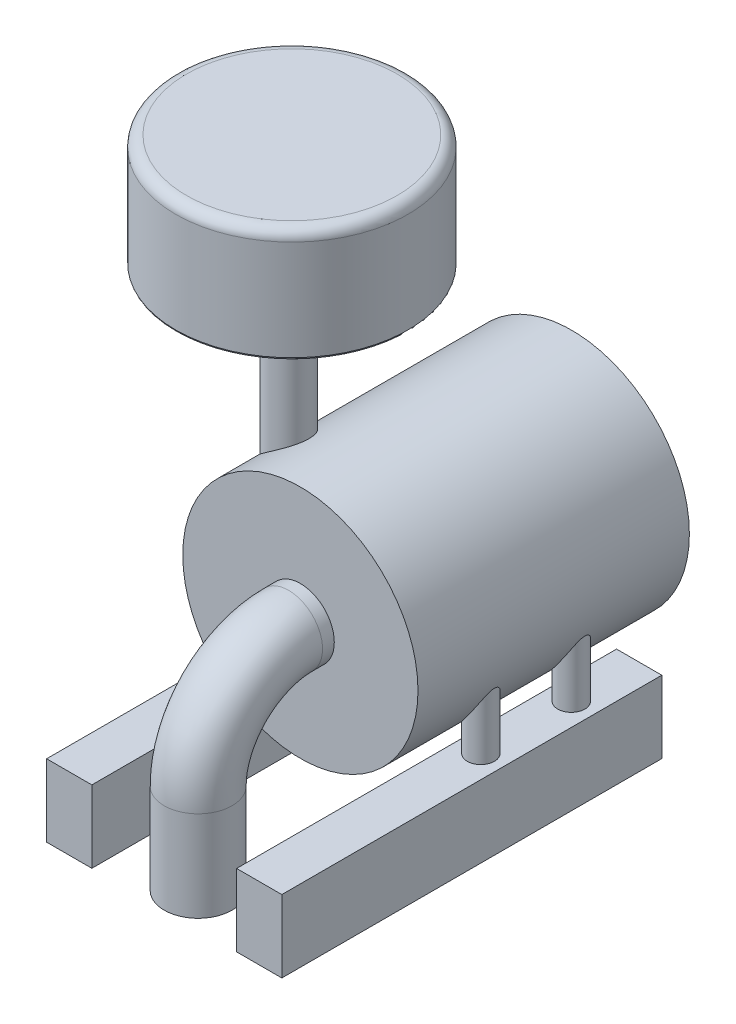
SolidWorks part; units mm, degrees
ref_plane "Front Plane" through (0, 0, 0) normal (0, 0, 1) x (1, 0, 0)
ref_plane "Top Plane" through (0, 0, 0) normal (0, 1, 0) x (1, 0, 0)
ref_plane "Right Plane" through (0, 0, 0) normal (1, 0, 0) x (0, 0, -1)
sketch "Sketch1" plane through (0, 0, 0) normal (0, 0, 1) x (1, 0, 0)
  circle A0 centre (0, 0) radius 130
  dimension "D1" = 260
extrude "Boss-Extrude1" add sketch "Sketch1" along normal blind 300
sketch "Sketch2" plane through (0, 0, 300) normal (0, 0, 1) x (1, 0, 0)
  circle A0 centre (0, 0) radius 37.5
  dimension "D1" = 75
extrude "Boss-Extrude2" add sketch "Sketch2" along normal blind 13
sketch "Sketch3" plane through (0, 0, 0) normal (0, 0, -1) x (-1, 0, 0)
  circle A0 centre (0, 0) radius 72
  circle A1 centre (0, 0) radius 117
  circle A2 centre (0, 0) radius 130 construction
  dimension "D1" = 13
  dimension "D2" = 45
extrude "Cut-Extrude1" cut sketch "Sketch3" against normal blind 13 draft 30
sketch "Sketch4" plane through (0, 0, 0) normal (0, 0, -1) x (-1, 0, 0)
  circle A0 centre (0, 0) radius 22.5
  dimension "D1" = 45
extrude "Boss-Extrude3" add sketch "Sketch4" along normal blind 7 draft 30
sketch "Sketch5" plane through (0, 0, 0) normal (0, 1, 0) x (1, 0, 0)
  line L0 (-37.5, -313) -> (37.5, -313) construction
  circle A0 centre (-75, -238) radius 22.5
  dimension "D1" = 45
  dimension "D2" = 75
  dimension "D3" = 75
extrude "Boss-Extrude4" add sketch "Sketch5" against normal up to surface (193.8162 mm away) from offset 300
sketch "Sketch7" plane through (0, 0, 313) normal (0, 0, 1) x (1, 0, 0)
  circle A1 centre (0, 0) radius 37.5
  circle A2 centre (0, 0) radius 37.5
  dimension "D1" = 0
sketch "Sketch8" plane through (0, 0, 0) normal (1, 0, 0) x (0, 0, -1)
  line L0 (-313, 0) -> (-307.3372, 0) construction
  line L1 (-313, 37.5) -> (-313, -37.5) construction
  line L2 (-413, -100) -> (-413, -200)
  arc A0 (-313, 0) -> (-413, -100) centre (-313, -100) ccw
  dimension "D1" = 100
  dimension "D2" = 100
sweep "Sweep1" add profiles "Sketch7" path "Sketch8"
sketch "Sketch9" plane through (0, 0, 0) normal (0, 1, 0) x (1, 0, 0)
  line L0 (-130, 0) -> (-130, -300) construction
  line L1 (-130, -30.5) -> (-80, -30.5)
  line L2 (-130, -30.5) -> (-130, -450.5)
  line L3 (-130, -450.5) -> (-80, -450.5)
  line L4 (-80, -30.5) -> (-80, -450.5)
  circle A3 centre (0, -413) radius 37.5 construction
  dimension "D1" = 50
  dimension "D2" = 420
extrude "Boss-Extrude5" add sketch "Sketch9" against normal blind 79.88 from offset 120 separate body offset against normal yes
sketch "Sketch10" plane through (0, -120, 0) normal (0, 1, 0) x (1, 0, 0)
  line L0 (-105, -30.5) -> (-105, -450.5) construction
  line L1 (-80, -30.5) -> (-130, -30.5) construction
  line L2 (-130, -450.5) -> (-80, -450.5) construction
  circle A0 centre (-105, -105.5) radius 15
  circle A1 centre (-105, -205.5) radius 15
  dimension "D1" = 30
  dimension "D2" = 75
  dimension "D3" = 100
extrude "Boss-Extrude6" add sketch "Sketch10" along normal up to next
mirror "Mirror2" about plane through (0, 0, 0) normal (1, 0, 0) of "Boss-Extrude5", "Boss-Extrude6"
sketch "Sketch11" plane through (0, 300, 0) normal (0, 1, 0) x (1, 0, 0)
  point P0 (-71.41, -237.8138)
ref_plane "Plane2" through (-71.41, 0, 0) normal (-1, 0, 0) x (0, 0, 1)
sketch "Sketch12" plane through (-71.41, 0, 0) normal (-1, 0, 0) x (0, 0, 1)
  line L0 (260.5, 300) -> (215.5, 300) construction
  line L1 (238, 300) -> (310.4381, 300)
  line L29 (238, 300) -> (238, 400.3837)
  line L30 (238, 400.3837) -> (354.4086, 400.3837)
  line L31 (366.4086, 388.3837) -> (366.4086, 277.7143)
  arc A1 (310.4381, 300) -> (311.202, 299.9961) centre (310.4381, 225) cw
  arc A4 (311.202, 299.9961) -> (362.9108, 276.3889) centre (310.489, 229.9997) cw
  arc A8 (362.9108, 276.3889) -> (366.4086, 277.7143) centre (364.4086, 277.7143) ccw
  arc A9 (354.4086, 400.3837) -> (366.4086, 388.3837) centre (354.4086, 388.3837) cw
  dimension "D1" = 2
  dimension "D2" = 70
  dimension "D4" = 75
  dimension "D3" = 12
revolve "Revolve1" add sketch "Sketch12" angle 360 about L29
shell "Shell1" thickness 2
